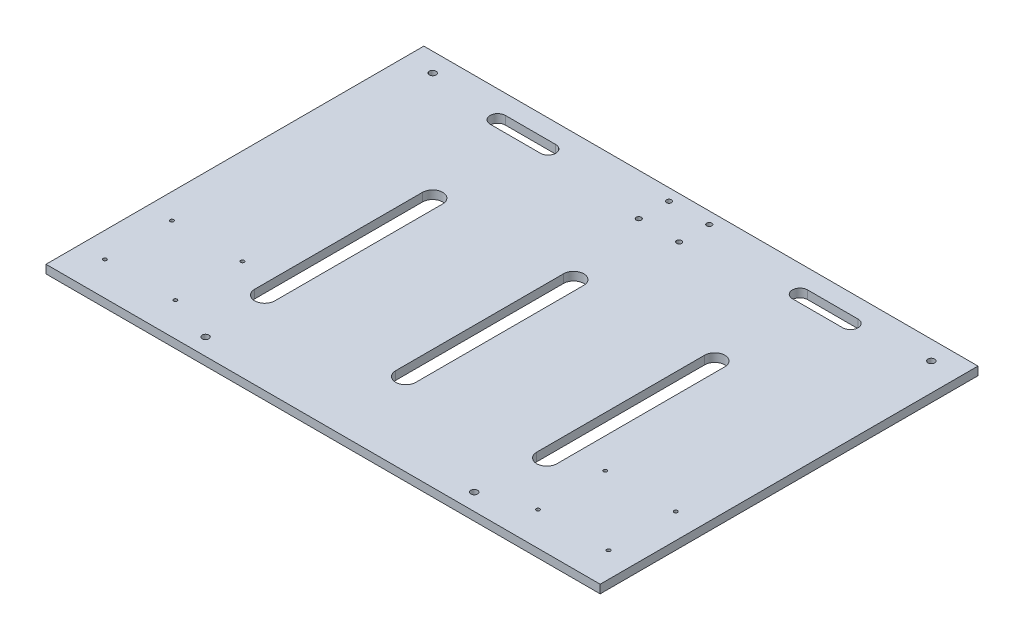
SolidWorks part; units mm, degrees
ref_plane "前视基准面" through (0, 0, 0) normal (0, 0, 1) x (1, 0, 0)
ref_plane "上视基准面" through (0, 0, 0) normal (0, 1, 0) x (1, 0, 0)
ref_plane "右视基准面" through (0, 0, 0) normal (1, 0, 0) x (0, 0, -1)
sketch "草图1" plane through (0, 0, 0) normal (0, 1, 0) x (1, 0, 0)
  line L1 (-15.2985, 237.1784) -> (314.7015, 237.1784)
  line L2 (-15.2985, 237.1784) -> (-15.2985, 12.1784)
  line L3 (-15.2985, 12.1784) -> (314.7015, 12.1784)
  line L4 (314.7015, 237.1784) -> (314.7015, 12.1784)
  dimension "D1" = 330
  dimension "D2" = 225
extrude "凸台-拉伸1" add sketch "草图1" along normal blind 5
sketch "草图2" plane through (0, 5, 0) normal (0, 1, 0) x (1, 0, 0)
  line L0 (149.7015, 237.1784) -> (149.7015, 12.1784) construction
  line L1 (314.7015, 237.1784) -> (-15.2985, 237.1784) construction
  line L2 (-15.2985, 12.1784) -> (314.7015, 12.1784) construction
  line L3 (137.7015, 230.1784) -> (137.7015, 206.5288) construction
  line L4 (137.7015, 230.1784) -> (161.7015, 212.1784) construction
  line L5 (161.7015, 230.1784) -> (137.7015, 212.1784) construction
  line L6 (149.7015, 221.1784) -> (50149.7015, 221.1784) construction
  line L7 (44.7015, 221.1784) -> (74.7015, 221.1784) construction
  line L8 (44.7015, 225.7154) -> (74.7015, 225.7154)
  line L9 (44.7015, 216.6414) -> (74.7015, 216.6414)
  line L10 (254.7015, 221.1784) -> (224.7015, 221.1784) construction
  line L11 (254.7015, 225.7154) -> (224.7015, 225.7154)
  line L12 (254.7015, 216.6414) -> (224.7015, 216.6414)
  circle A0 centre (137.7015, 230.1784) radius 1.515
  circle A1 centre (161.7015, 230.1784) radius 1.515
  circle A2 centre (137.7015, 212.1784) radius 1.515
  circle A3 centre (161.7015, 212.1784) radius 1.515
  arc A4 (44.7015, 225.7154) -> (44.7015, 216.6414) centre (44.7015, 221.1784) ccw
  arc A5 (74.7015, 216.6414) -> (74.7015, 225.7154) centre (74.7015, 221.1784) ccw
  arc A6 (254.7015, 225.7154) -> (254.7015, 216.6414) centre (254.7015, 221.1784) cw
  arc A7 (224.7015, 216.6414) -> (224.7015, 225.7154) centre (224.7015, 221.1784) cw
  point P14 (149.7015, 221.1784)
  point P20 (59.7015, 221.1784)
  point P27 (239.7015, 221.1784)
  dimension "D1" = 3.03
  dimension "D2" = 24
  dimension "D3" = 18
  dimension "D4" = 18
  dimension "D5" = 24
  dimension "D6" = 7
  dimension "D7" = 30
  dimension "D8" = 90
extrude "切除-拉伸1" cut sketch "草图2" against normal through all
sketch "草图3" plane through (0, 5, 0) normal (0, 1, 0) x (1, 0, 0)
  line L0 (-14.3127, 52.1784) -> (315.6873, 52.1784) construction
  line L1 (-15.2985, 237.1784) -> (-15.2985, 12.1784) construction
  line L2 (-15.2985, 12.1784) -> (314.7015, 12.1784) construction
  line L3 (314.7015, 12.1784) -> (314.7015, 237.1784) construction
  line L4 (149.7015, 462.1784) -> (149.7015, 12.1784) construction
  circle A0 centre (-0.2985, 32.1784) radius 1.05
  circle A1 centre (-0.2985, 72.1784) radius 1.05
  circle A2 centre (41.7015, 32.1784) radius 1.05
  circle A3 centre (41.7015, 72.1784) radius 1.05
  circle A4 centre (257.7015, 72.1784) radius 1.05
  circle A5 centre (257.7015, 32.1784) radius 1.05
  circle A6 centre (299.7015, 72.1784) radius 1.05
  circle A7 centre (299.7015, 32.1784) radius 1.05
  point P15 (149.7015, 237.1784)
  dimension "D1" = 40
  dimension "D2" = 42
  dimension "D3" = 20
  dimension "D4" = 15
extrude "切除-拉伸2" cut sketch "草图3" against normal through all
sketch "草图5" plane through (0, 5, 0) normal (0, 1, 0) x (1, 0, 0)
  line L0 (149.7015, 237.1784) -> (149.7015, -49762.8216) construction
  line L1 (314.7015, 237.1784) -> (-15.2985, 237.1784) construction
  line L2 (-28.7911, 85.1784) -> (354.7976, 85.1784) construction
  line L3 (149.7015, 161.4116) -> (149.7015, 61.4116) construction
  line L4 (155.7015, 161.4116) -> (155.7015, 61.4116)
  line L5 (143.7015, 161.4116) -> (143.7015, 61.4116)
  line L6 (233.7015, 161.4116) -> (233.7015, 61.4116) construction
  line L7 (239.7015, 161.4116) -> (239.7015, 61.4116)
  line L8 (227.7015, 161.4116) -> (227.7015, 61.4116)
  line L9 (65.7015, 161.4116) -> (65.7015, 61.4116) construction
  line L10 (59.7015, 161.4116) -> (59.7015, 61.4116)
  line L11 (71.7015, 161.4116) -> (71.7015, 61.4116)
  arc A0 (155.7015, 161.4116) -> (143.7015, 161.4116) centre (149.7015, 161.4116) ccw
  arc A1 (143.7015, 61.4116) -> (155.7015, 61.4116) centre (149.7015, 61.4116) ccw
  arc A2 (239.7015, 161.4116) -> (227.7015, 161.4116) centre (233.7015, 161.4116) ccw
  arc A3 (227.7015, 61.4116) -> (239.7015, 61.4116) centre (233.7015, 61.4116) ccw
  arc A4 (59.7015, 161.4116) -> (71.7015, 161.4116) centre (65.7015, 161.4116) cw
  arc A5 (71.7015, 61.4116) -> (59.7015, 61.4116) centre (65.7015, 61.4116) cw
  point P4 (149.7015, 237.1784)
  point P9 (149.7015, 111.4116)
  point P17 (233.7015, 111.4116)
  point P23 (65.7015, 111.4116)
  point P28 (0, 0)
  point P29 (0, 0)
  point P30 (149.7015, 111.4116)
  dimension "D3" = 6
  dimension "D1" = 152
  dimension "D2" = 100
  dimension "D5" = 84
  dimension "D4" = 2
extrude "切除-拉伸4" cut sketch "草图5" against normal through all
sketch "草图6" plane through (0, 5, 0) normal (0, 1, 0) x (1, 0, 0)
  line L0 (314.7015, 12.1784) -> (-15.2985, 237.1784) construction
  line L1 (314.7015, 237.1784) -> (-15.2985, 12.1784) construction
  line L2 (149.7015, 237.1784) -> (149.7015, 50237.1784) construction
  line L3 (314.7015, 237.1784) -> (-15.2985, 237.1784) construction
  line L4 (149.7015, 22.1784) -> (-49850.2985, 22.1784) construction
  line L5 (-15.2985, 12.1784) -> (314.7015, 12.1784) construction
  circle A0 centre (1.226, 225.9117) radius 2
  circle A1 centre (298.1769, 225.9117) radius 2
  circle A2 centre (69.7015, 22.1784) radius 2
  circle A3 centre (229.7015, 22.1784) radius 2
  point P14 (149.7015, 237.1784)
  dimension "D1" = 4
  dimension "D4" = 4
  dimension "D2" = 20
  dimension "D3" = 10
  dimension "D5" = 80
extrude "切除-拉伸5" cut sketch "草图6" against normal through all
